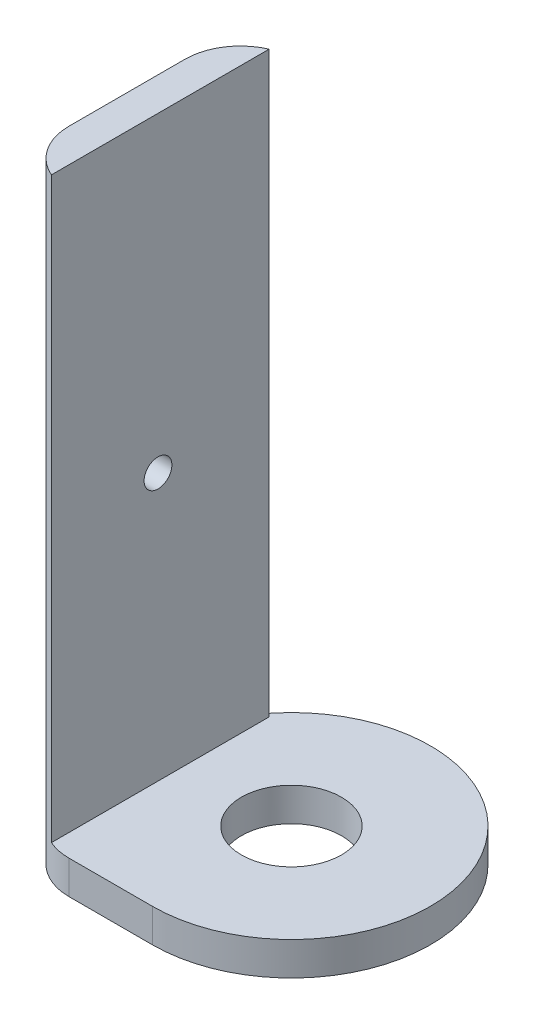
SolidWorks part; units mm, degrees
ref_plane "Front Plane" through (0, 0, 0) normal (0, 0, 1) x (1, 0, 0)
ref_plane "Top Plane" through (0, 0, 0) normal (0, 1, 0) x (1, 0, 0)
ref_plane "Right Plane" through (0, 0, 0) normal (1, 0, 0) x (0, 0, -1)
sketch "Sketch1" plane through (0, 0, 0) normal (0, 1, 0) x (1, 0, 0)
  line L0 (-12.5, -12.5) -> (0, -12.5) construction
  line L5 (-12.5, 12.5) -> (0, 12.5) construction
  line L6 (-12.5, 12.5) -> (-12.5, -12.5) construction
  line L7 (-12.5, -12.5) -> (-12.5, 7.5)
  line L9 (-12.5, -12.5) -> (0, -12.5)
  line L10 (-12.5, 7.5) -> (-9.5, 7.5)
  line L11 (-9.5, 7.5) -> (-9.5, -12.5)
  circle A0 centre (0, 0) radius 12.5
  point P0 (0, 0)
  dimension "D1" = 25
  dimension "D2" = 20
  dimension "D3" = 3
extrude "Boss-Extrude1" add sketch "Sketch1" along normal blind 3 contours A0 L11 L9 | A0 L7 L9 L11 | A0 L10 L7 | A0 region at (-11.2298, 0, 8.7729) region at (-11.7649, 0, -5.6646) region at (-7.2162, 0, 11.2388)
extrude "Boss-Extrude3" add sketch "Sketch1<4>" along normal blind 55 contours L10 A0 L11 | A0 L10 L7 | A0 L7 L9 L11 region at (-11.2298, 0, 8.7729) region at (-11.7649, 0, -5.6646) region at (-10.7183, 0, 0.037)
sketch "Sketch1<4>" plane through (0, 0, 0) normal (0, 1, 0) x (1, 0, 0) same geometry as "Sketch1"
sketch "Sketch2" plane through (-12.5, 0, 0) normal (-1, 0, 0) x (0, 0, 1)
  line L0 (2.5, 55) -> (2.5, 27) construction
  line L1 (12.5, 55) -> (-7.5, 55) construction
  dimension "D1" = 28
hole_wizard "M8 Clearance Hole1" positions "Sketch3" profile "Sketch4" hole size "M8" standard "ANSI Metric" end condition through all
sketch "Sketch3" plane through (0, 0, 0) normal (0, -1, 0) x (-1, 0, 0)
  point P0 (0, 0)
sketch "Sketch4" plane through (0, 0, 0) normal (1, 0, 0) x (0, 0, -1)
  line L0 (0, 0) -> (0, 55)
  line L1 (0, 55) -> (4.5, 55)
  line L2 (4.5, 55) -> (4.5, 0)
  line L5 (4.5, 0) -> (0, 0)
  line L11 (0, -6.35) -> (0, 107.95) construction
  dimension "Thru Hole Dia." = 9
  dimension "Thru Hole Depth" = 55
hole_wizard "Tap Drill for M3x0.5 Tap1" positions "Sketch5" profile "Sketch6" hole size "M3x0.5" standard "ANSI Metric" end condition through all
sketch "Sketch5" plane through (-12.5, 0, 0) normal (-1, 0, 0) x (0, 0, 1)
  point P0 (2.5, 27)
sketch "Sketch6" plane through (-12.5, 27, 2.5) normal (0, 1, 0) x (0, 0, 1)
  line L0 (0, 0) -> (0, 25)
  line L1 (0, 25) -> (1.25, 25)
  line L2 (1.25, 25) -> (1.25, 0)
  line L5 (1.25, 0) -> (0, 0)
  line L11 (0, -6.35) -> (0, 107.95) construction
  dimension "Thru Hole Dia." = 2.5
  dimension "Thru Hole Depth" = 25
fillet "Fillet1" radius 5 2 edges at (-12.5, 27.5, 12.5) (-12.5, 27.5, -7.5)
